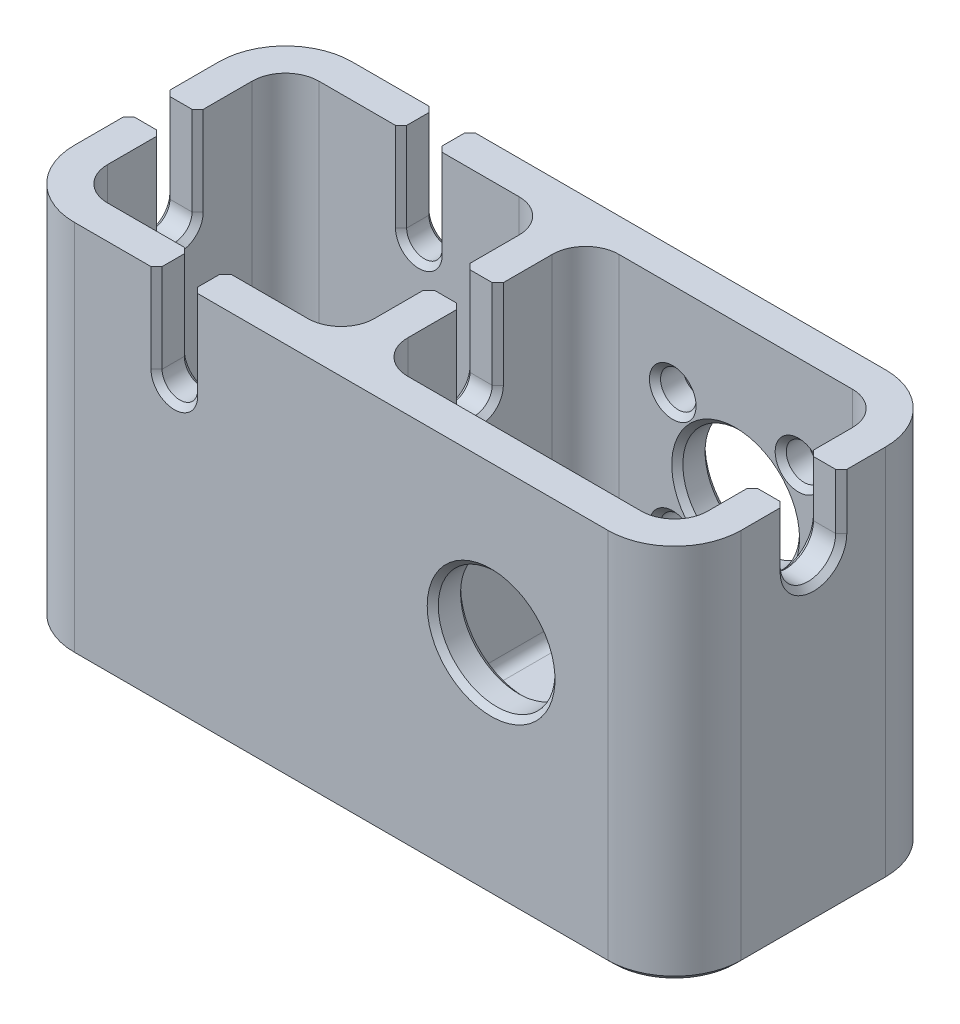
SolidWorks part; units mm, degrees
ref_plane "Front Plane" through (0, 0, 0) normal (0, 0, 1) x (1, 0, 0)
ref_plane "Top Plane" through (0, 0, 0) normal (0, 1, 0) x (1, 0, 0)
ref_plane "Right Plane" through (0, 0, 0) normal (1, 0, 0) x (0, 0, -1)
sketch "Sketch1" plane through (0, 0, 0) normal (0, 1, 0) x (1, 0, 0)
  line L1 (0, 0) -> (60, 0)
  line L2 (0, 0) -> (0, 25)
  line L3 (0, 25) -> (60, 25)
  line L4 (60, 0) -> (60, 25)
  dimension "D1" = 25
  dimension "D2" = 60
extrude "Boss-Extrude1" add sketch "Sketch1" along normal blind 4
sketch "Sketch3" plane through (0, 4, 0) normal (0, 1, 0) x (1, 0, 0)
  line L0 (0, 25) -> (0, 0) construction
  line L1 (60, 25) -> (0, 25) construction
  circle A0 centre (7.5, 17.5) radius 1.6
  circle A1 centre (22.5, 17.5) radius 1.6
  circle A2 centre (22.5, 7.5) radius 1.6
  circle A3 centre (7.5, 7.5) radius 1.6
  dimension "D1" = 3.2
  dimension "D2" = 10
  dimension "D3" = 15
  dimension "D4" = 7.5
  dimension "D5" = 7.5
extrude "Cut-Extrude1" cut sketch "Sketch3" against normal through all
sketch "Sketch4" plane through (0, 4, 0) normal (0, 1, 0) x (1, 0, 0)
  line L0 (27, 22) -> (27, 3)
  line L1 (0, 25) -> (60, 25)
  line L2 (0, 25) -> (0, 0)
  line L3 (0, 0) -> (60, 0)
  line L4 (60, 25) -> (60, 0)
  line L5 (3, 22) -> (27, 22)
  line L6 (3, 22) -> (3, 3)
  line L7 (3, 3) -> (27, 3)
  line L8 (57, 22) -> (57, 3)
  line L9 (30, 22) -> (30, 3)
  line L10 (30, 22) -> (57, 22)
  line L11 (30, 3) -> (57, 3)
  dimension "D1" = 3
  dimension "D2" = 3
  dimension "D3" = 3
  dimension "D4" = 3
  dimension "D5" = 24
  dimension "D6" = 3
extrude "Boss-Extrude2" add sketch "Sketch4" along normal blind 30
sketch "Sketch5" plane through (0, 0, -25) normal (0, 0, -1) x (-1, 0, 0)
  line L0 (-60, 0) -> (0, 0) construction
  line L1 (-57, 34) -> (-30, 34) construction
  circle A0 centre (-43.5, 20) radius 5.25
  point P8 (-43.5, 34)
  dimension "D1" = 10.5
  dimension "D2" = 20
extrude "Cut-Extrude2" cut sketch "Sketch5" against normal through all
sketch "Sketch6" plane through (0, 0, -25) normal (0, 0, -1) x (-1, 0, 0)
  line L0 (-37.8431, 14.3431) -> (-49.1569, 25.6569) construction
  line L1 (-49.1569, 14.3431) -> (-37.8431, 25.6569) construction
  line L2 (-43.5, 14.75) -> (-43.5, 25.25) construction
  line L3 (-38.25, 20) -> (-48.75, 20) construction
  circle A0 centre (-37.8431, 14.3431) radius 1.6
  circle A1 centre (-49.1569, 14.3431) radius 1.6
  circle A2 centre (-49.1569, 25.6569) radius 1.6
  circle A3 centre (-37.8431, 25.6569) radius 1.6
  circle A5 centre (-43.5, 20) radius 5.25 construction
  point P16 (-43.5, 20)
  point P17 (-43.5, 20)
  dimension "D3" = 3.2
  dimension "D1" = 90
  dimension "D2" = 8
extrude "Cut-Extrude3" cut sketch "Sketch6" against normal up to next
fillet "Fillet3" radius 3 8 edges at (30, 19, -3) (57, 19, -3) (27, 19, -3) (3, 19, -3) (3, 19, -22) (27, 19, -22) (57, 19, -22) (30, 19, -22)
fillet "Fillet4" radius 1 16 edges at (56.1213, 4, -3.8787) (43.5, 4, -3) (30.8787, 4, -3.8787) (30, 4, -12.5) (30.8787, 4, -21.1213) (43.5, 4, -22) (56.1213, 4, -21.1213) (26.1213, 4, -3.8787) (15, 4, -3) (3.8787, 4, -3.8787) (3, 4, -12.5) (3.8787, 4, -21.1213) (15, 4, -22) (26.1213, 4, -21.1213) (57, 4, -12.5) (27, 4, -12.5)
fillet "Fillet5" radius 6 4 edges at (60, 17, 0) (60, 17, -25) (0, 17, 0) (0, 17, -25)
sketch "Sketch7" plane through (0, 0, -25) normal (0, 0, -1) x (-1, 0, 0)
  line L0 (-13.4, 26) -> (-13.4, 34)
  line L1 (-54, 34) -> (-6, 34) construction
  line L2 (-13.4, 34) -> (-16.6, 34)
  line L3 (-16.6, 34) -> (-16.6, 26)
  line L5 (-24, 34) -> (-6, 34) construction
  arc A0 (-16.6, 26) -> (-13.4, 26) centre (-15, 26) ccw
  point P1 (-15, 34)
  point P10 (-15, 34)
  dimension "D1" = 1.6
  dimension "D2" = 8
extrude "Cut-Extrude4" cut sketch "Sketch7" against normal through all
sketch "Sketch8" plane through (0, 0, 0) normal (-1, 0, 0) x (0, 0, 1)
  line L0 (-14.1, 26) -> (-14.1, 34)
  line L1 (-19, 34) -> (-6, 34) construction
  line L2 (-14.1, 34) -> (-10.9, 34)
  line L3 (-10.9, 34) -> (-10.9, 26)
  line L4 (-19, 34) -> (-6, 34) construction
  arc A0 (-14.1, 26) -> (-10.9, 26) centre (-12.5, 26) ccw
  point P1 (-12.5, 34)
  point P10 (-12.5, 34)
  dimension "D2" = 1.6
  dimension "D1" = 8
extrude "Cut-Extrude5" cut sketch "Sketch8" against normal up to surface (30 mm away) up to face at (30, 19.5, -12.5)
sketch "Sketch9" plane through (60, 0, 0) normal (1, 0, 0) x (0, 0, -1)
  line L0 (15, 29) -> (15, 34)
  line L1 (6, 34) -> (19, 34) construction
  line L2 (15, 34) -> (10, 34)
  line L3 (10, 34) -> (10, 29)
  line L4 (6, 34) -> (19, 34) construction
  arc A0 (10, 29) -> (15, 29) centre (12.5, 29) ccw
  point P1 (12.5, 34)
  point P10 (12.5, 34)
  dimension "D2" = 2.5
  dimension "D1" = 5
extrude "Cut-Extrude6" cut sketch "Sketch9" against normal up to next
chamfer "Chamfer1" distance 0.5 angle 45 12 edges at (58.2426, 0, -23.2426) (30, 0, -25) (1.7574, 0, -23.2426) (0, 0, -12.5) (1.7574, 0, -1.7574) (30, 0, 0) (58.2426, 0, -1.7574) (60, 0, -12.5) (7.5, 0, -15.9) (22.5, 0, -15.9) (22.5, 0, -5.9) (7.5, 0, -5.9)
chamfer "Chamfer2" distance 0.5 angle 45 12 edges at (38.25, 20, -3) (38.25, 20, 0) (50.7569, 25.6569, -22) (50.7569, 14.3431, -22) (39.4431, 14.3431, -22) (48.75, 20, -22) (39.4431, 25.6569, -22) (36.2431, 25.6569, -25) (47.5569, 25.6569, -25) (47.5569, 14.3431, -25) (38.25, 20, -25) (36.2431, 14.3431, -25)
chamfer "Chamfer3" distance 0.5 angle 45 30 edges at (57, 31.5, -10) (57, 31.5, -15) (57, 26.5, -12.5) (60, 31.5, -10) (60, 31.5, -15) (60, 26.5, -12.5) (30, 30, -14.1) (30, 30, -10.9) (30, 24.4, -12.5) (27, 30, -14.1) (27, 30, -10.9) (27, 24.4, -12.5) (16.6, 30, -25) (13.4, 30, -25) (15, 24.4, -25) (13.4, 30, -22) (16.6, 30, -22) (15, 24.4, -22) (0, 30, -14.1) (0, 30, -10.9) (0, 24.4, -12.5) (3, 30, -10.9) (3, 30, -14.1) (3, 24.4, -12.5) (16.6, 30, 0) (13.4, 30, 0) (15, 24.4, 0) (16.6, 30, -3) (13.4, 30, -3) (15, 24.4, -3)
chamfer "Chamfer4" distance 0.5 angle 45 4 edges at (7.5, 4, -5.9) (22.5, 4, -5.9) (22.5, 4, -15.9) (7.5, 4, -15.9)
